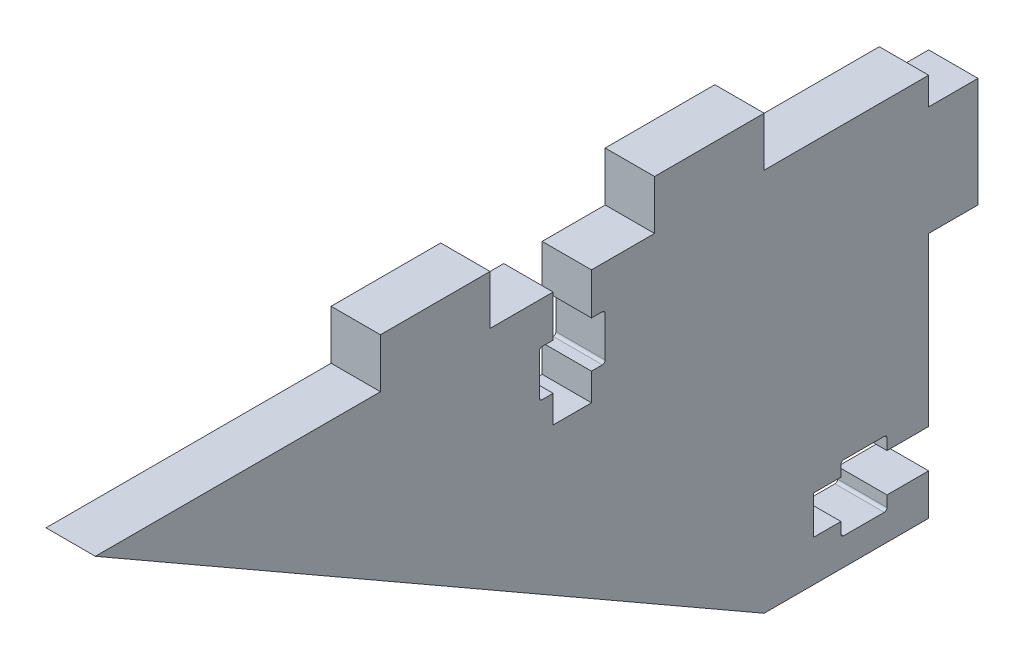
SolidWorks part; units mm, degrees
ref_plane "Front Plane" through (0, 0, 0) normal (0, 0, 1) x (1, 0, 0)
ref_plane "Top Plane" through (0, 0, 0) normal (0, 1, 0) x (1, 0, 0)
ref_plane "Right Plane" through (0, 0, 0) normal (1, 0, 0) x (0, 0, -1)
sketch "Sketch1" plane through (0, 0, 0) normal (1, 0, 0) x (0, 0, -1)
  line L0 (0, 0) -> (0, -35)
  line L1 (0, -35) -> (-76, 0)
  line L2 (-76, 0) -> (0, 0)
  dimension "D1" = 35
  dimension "D2" = 76
extrude "Boss-Extrude1" add sketch "Sketch1" along normal blind 4.5
sketch "Sketch2" plane through (4.5, 0, 0) normal (1, 0, 0) x (0, 0, -1)
  line L0 (0, -35) -> (0, 0) construction
  line L1 (-4.5, -2.5) -> (4.5, -2.5)
  line L2 (-4.5, -2.5) -> (-4.5, -12.5)
  line L3 (-4.5, -12.5) -> (4.5, -12.5)
  line L4 (4.5, -2.5) -> (4.5, -12.5)
  line L5 (-4.5, -2.5) -> (4.5, -12.5) construction
  line L6 (-4.5, -12.5) -> (4.5, -2.5) construction
  line L7 (0, 0) -> (-76, 0) construction
  point P0 (0, -7.5)
  dimension "D2" = 7.5
  dimension "D3" = 4.5
extrude "Boss-Extrude2" add sketch "Sketch2" against normal through all
sketch "Sketch3" plane through (4.5, 0, 0) normal (1, 0, 0) x (0, 0, -1)
  line L0 (0, -35) -> (-15, -35)
  line L1 (0, -25) -> (-76, 0)
  line L4 (0, -35) -> (0, -12.5) construction
  line L5 (0, -25) -> (0, -35)
  line L6 (-76, 0) -> (-15, -35)
  dimension "D1" = 15
  dimension "D2" = 10
extrude "Boss-Extrude3" add sketch "Sketch3" against normal through all
sketch "Sketch4" plane through (4.5, 0, 0) normal (1, 0, 0) x (0, 0, -1)
  line L0 (0, -29.5) -> (-10.5, -29.5) construction
  line L1 (0, -35) -> (0, -12.5) construction
  line L2 (0, -27.75) -> (-10.5, -27.75) construction
  line L3 (-10.5, -27.75) -> (-10.5, -31.25) construction
  line L4 (0, -31.25) -> (0, -27.75)
  line L5 (0, -27.75) -> (-3.8, -27.75)
  line L6 (-3.8, -27.75) -> (-3.8, -26.75)
  line L7 (-4.05, -26.5) -> (-7.75, -26.5)
  line L8 (-8, -26.75) -> (-8, -27.75)
  line L9 (-8, -27.75) -> (-10.5, -27.75)
  line L10 (-10.5, -27.75) -> (-10.5, -31.25)
  line L12 (0, -31.25) -> (-10.5, -31.25) construction
  line L13 (-8, -31.25) -> (-10.5, -31.25)
  line L14 (-8, -32.25) -> (-8, -31.25)
  line L15 (-4.05, -32.5) -> (-7.75, -32.5)
  line L16 (-3.8, -31.25) -> (-3.8, -32.25)
  line L17 (0, -31.25) -> (-3.8, -31.25)
  line L18 (4.5, -12.5) -> (4.5, -2.5) construction
  line L19 (0, -18.5) -> (-43.7571, -18.5) construction
  line L20 (-76, 0) -> (-15, -35) construction
  line L37 (0, -31.25) -> (-10.5, -31.25) construction
  arc A0 (-8, -32.25) -> (-7.75, -32.5) centre (-7.75, -32.25) ccw
  arc A1 (-4.05, -32.5) -> (-3.8, -32.25) centre (-4.05, -32.25) ccw
  arc A2 (-3.8, -26.75) -> (-4.05, -26.5) centre (-4.05, -26.75) ccw
  arc A3 (-7.75, -26.5) -> (-8, -26.75) centre (-7.75, -26.75) ccw
  point P10 (4.5, -7.5)
  point P20 (-8, -32.5)
  point P23 (-3.8, -32.5)
  point P26 (-3.8, -26.5)
  point P29 (-8, -26.5)
  dimension "D7" = 0.25
  dimension "D1" = 10.5
  dimension "D2" = 1.75
  dimension "D3" = 3
  dimension "D4" = 4.2
  dimension "D5" = 8
  dimension "D6" = 22
extrude "Cut-Extrude1" cut sketch "Sketch4" against normal through all
sketch "Sketch5" plane through (4.5, 0, 0) normal (1, 0, 0) x (0, 0, -1)
  line L0 (0, 0) -> (-76, 0) construction
  line L1 (-25, 4.5) -> (-15, 4.5)
  line L2 (-25, 4.5) -> (-25, -4.5)
  line L3 (-25, -4.5) -> (-15, -4.5)
  line L4 (-15, 4.5) -> (-15, -4.5)
  line L5 (-25, 4.5) -> (-15, -4.5) construction
  line L6 (-25, -4.5) -> (-15, 4.5) construction
  line L7 (-32.5, 0) -> (-32.5, 4.5) construction
  line L8 (-40, -4.5) -> (-50, 4.5) construction
  line L9 (-40, 4.5) -> (-50, -4.5) construction
  line L10 (-50, 4.5) -> (-50, -4.5)
  line L11 (-40, -4.5) -> (-50, -4.5)
  line L12 (-40, 4.5) -> (-40, -4.5)
  line L13 (-40, 4.5) -> (-50, 4.5)
  line L14 (-25, -4.5) -> (-15, 4.5) construction
  point P0 (-20, 0)
  point P14 (-45, 0)
  dimension "D3" = 4.5
  dimension "D1" = 20
  dimension "D2" = 10
  dimension "D4" = 25
extrude "Boss-Extrude4" add sketch "Sketch5" against normal through all
sketch "Sketch6" plane through (4.5, 0, 0) normal (1, 0, 0) x (0, 0, -1)
  line L0 (-32.5, 0) -> (-32.5, -10.5) construction
  line L1 (-25, 0) -> (-40, 0) construction
  line L2 (-30.75, -10.5) -> (-34.25, -10.5) construction
  line L3 (-34.25, -10.5) -> (-34.25, 0) construction
  line L4 (-30.75, 0) -> (-34.25, 0)
  line L5 (-34.25, 0) -> (-34.25, -3.8)
  line L6 (-34.25, -3.8) -> (-35.25, -3.8)
  line L7 (-35.5, -4.05) -> (-35.5, -7.75)
  line L8 (-35.25, -8) -> (-34.25, -8)
  line L9 (-34.25, -8) -> (-34.25, -10.5)
  line L10 (-34.25, -10.5) -> (-30.75, -10.5)
  line L11 (-30.75, -10.5) -> (-30.75, 0) construction
  line L12 (-30.75, -8) -> (-30.75, -10.5)
  line L13 (-29.75, -8) -> (-30.75, -8)
  line L14 (-29.5, -4.05) -> (-29.5, -7.75)
  line L15 (-30.75, -3.8) -> (-29.75, -3.8)
  line L16 (-30.75, 0) -> (-30.75, -3.8)
  arc A0 (-35.5, -7.75) -> (-35.25, -8) centre (-35.25, -7.75) ccw
  arc A1 (-35.25, -3.8) -> (-35.5, -4.05) centre (-35.25, -4.05) ccw
  arc A2 (-29.75, -3.8) -> (-29.5, -4.05) centre (-29.75, -4.05) cw
  arc A3 (-29.5, -7.75) -> (-29.75, -8) centre (-29.75, -7.75) cw
  point P12 (-35.5, -8)
  point P15 (-35.5, -3.8)
  point P26 (-29.5, -3.8)
  point P27 (-29.5, -8)
  dimension "D1" = 10.5
  dimension "D2" = 1.75
  dimension "D4" = 4.2
  dimension "D6" = 0.25
  dimension "D3" = 8
  dimension "D5" = 3
extrude "Cut-Extrude2" cut sketch "Sketch6" against normal through all
equation "\"X-ROD-SPACING\"=45"
equation "\"Y-ROD-SPACING\"=75"
equation "\"Z-ROD-SPACING\"=17.5"
equation "\"Y-BED-OFFSET\"=2"
equation "\"Y-BED-ROD-INSET\"=3.5"
equation "\"Y-BED-SCREW-SPACING\"=209"
equation "\"Y-BED-SCREW-CUTOUT-SLOT-HEIGHT\"=2"
equation "\"T-SLOT-NUT-FILLET-RADIUS\"=0.25"
equation "\"T-SLOT-SCREW-SHAFT-RADIUS\"=1.75"
equation "\"T-SLOT-SCREW-SHAFT-CUTOUT-LENGTH\"=10.5"
equation "\"T-SLOT-NUT-DEPTH\"=4.2"
equation "\"T-SLOT-NUT-WIDTH\"=3"
equation "\"T-SLOT-NUT-END-DISTANCE\"=8"
equation "\"ACRYLIC-THICKNESS\"=10"
equation "\"ACRYLIC-THICKNESS2\"=4.5"
equation "\"ACRYLIC-TAB-CUTOUT-SIZE\"=\"ACRYLIC-THICKNESS\"+\"ACRYLIC-TAB-TOLERANCE\"*2"
equation "\"ACRYLIC-TAB-WIDTH\"=\"ACRYLIC-THICKNESS\""
equation "\"ACRYLIC-M3-HOLE\"=3.1"
equation "\"SMOOTHROD-CAP-SCREW-DISTANCE\"=20"
equation "\"FRAME-WIDTH-INNER\"=370"
equation "\"NEMA17-HOLE-SPACING\"=31"
equation "\"NEMA17-CENTRAL-CUTOUT\"=22.5"
equation "\"Z-BRACKET-REACH\"=55"
equation "\"Z-ROD-INSET\"=16"
equation "\"TOP-BRACKET-SPACING\"=40"
equation "\"SMOOTHROD-X-LENGTH\"=350"
equation "\"SMOOTHROD-Y-LENGTH\"=350"
equation "\"SMOOTHROD-Z-LENGTH\"=350"
equation "\"SMOOTHROD-TIGHTENING-HEADROOM\"=.25"
equation "\"LEADSCREW-Z-LENGTH\"=300"
equation "\"SCREW-LENGTH-FRAME\"=\"ACRYLIC-THICKNESS\" + 10"
equation "\"SCREW-LENGTH-MOTOR\"=\"ACRYLIC-THICKNESS\" + 5"
equation "\"SCREW-LENGTH-EXTRUDER\"=28"
equation "\"SCREW-HEAD-RADIUS\"=6"
equation "\"PRINTED-X-SMOOTHROD-DIAMETER\"=8.2"
equation "\"PRINTED-X-SMOOTHROD-CUTOUT\"=10"
equation "\"PRINTED-X-BASE-HEIGHT\"=10"
equation "\"PRINTED-LM8UU-CUTOUT-SIZE\"=15.25"
equation "\"PRINTED-LM8UU-CUTOUT-LENGTH\"=24.5"
equation "\"PRINTED-X-IDLER-HEIGHT\"=16"
equation "\"PSU-MOUNTING-WIDTH\"=95"
equation "\"PSU-MOUNTING-HEIGHT\"=177"
equation "\"Y-BELT-TO-ROD-DISTANCE\"=20"
equation "\"SPOOL-HOLDER-ROD-SPACING\"=150"
equation "\"ACRYLIC-X-CARRIAGE-WIDTH\"=55"
equation "\"ACRYLIC-X-CARRIAGE-HEIGHT\"=75"
equation "\"ACRYLIC-X-CARRIAGE-SCREW-SPACING-X\"=15"
equation "\"ACRYLIC-X-CARRIAGE-SCREW-SPACING-Y\"=33"
equation "\"ACRYLIC-X-CARRIAGE-CENTER-TAB-SPACING\"=14"
equation "\"ACRYLIC-X-CARRIAGE-EXTRUDER-SHELF-DEPTH\"=\"ACRYLIC-X-CARRIAGE-EXTRUDER-OFFSET\" + 28"
equation "\"D1@Boss-Extrude1\"=\"ACRYLIC-THICKNESS2\""
equation "\"D1@Sketch2\"=\"ACRYLIC-TAB-WIDTH\""
equation "\"D3@Sketch2\"=\"ACRYLIC-THICKNESS2\""
equation "\"ACRYLIC-X-CARRIAGE-LM8UU-CUTOUT-WIDTH\"=24.25"
equation "\"ACRYLIC-X-CARRIAGE-EXTRUDER-BRACE-SPACING\"=23"
equation "\"ACRYLIC-X-CARRIAGE-EXTRUDER-BRACE-HEIGHT\"=35"
equation "\"D1@Sketch1\"=\"ACRYLIC-X-CARRIAGE-EXTRUDER-BRACE-HEIGHT\""
equation "\"D1@Sketch4\"=\"T-SLOT-SCREW-SHAFT-CUTOUT-LENGTH\""
equation "\"D2@Sketch4\"=\"T-SLOT-SCREW-SHAFT-RADIUS\""
equation "\"D3@Sketch4\"=\"T-SLOT-NUT-WIDTH\""
equation "\"D4@Sketch4\"=\"T-SLOT-NUT-DEPTH\""
equation "\"D5@Sketch4\"=\"T-SLOT-NUT-END-DISTANCE\""
equation "\"D7@Sketch4\"=\"T-SLOT-NUT-FILLET-RADIUS\""
equation "\"ACRYLIC-X-CARRIAGE-EXTRUDER-BRACE-SCREW-SPACING\"=22"
equation "\"D6@Sketch4\"=\"ACRYLIC-X-CARRIAGE-EXTRUDER-BRACE-SCREW-SPACING\""
equation "\"ACRYLIC-X-CARRIAGE-EXTRUDER-BRACE-TAB-OFFSET\"=20"
equation "\"D1@Sketch5\"=\"ACRYLIC-X-CARRIAGE-EXTRUDER-BRACE-TAB-OFFSET\""
equation "\"D2@Sketch5\"=\"ACRYLIC-TAB-WIDTH\""
equation "\"D3@Sketch5\"=\"ACRYLIC-THICKNESS2\""
equation "\"ACRYLIC-X-CARRIAGE-EXTRUDER-OFFSET\"=26"
equation "\"ACRYLIC-X-CARRIAGE-EXTRUDER-ANGLE\"=90"
equation "\"D1@Sketch6\"=\"T-SLOT-SCREW-SHAFT-CUTOUT-LENGTH\""
equation "\"D2@Sketch6\"=\"T-SLOT-SCREW-SHAFT-RADIUS\""
equation "\"D3@Sketch6\"=\"T-SLOT-NUT-END-DISTANCE\""
equation "\"D4@Sketch6\"=\"T-SLOT-NUT-DEPTH\""
equation "\"D5@Sketch6\"=\"T-SLOT-NUT-WIDTH\""
equation "\"D6@Sketch6\"=\"T-SLOT-NUT-FILLET-RADIUS\""
